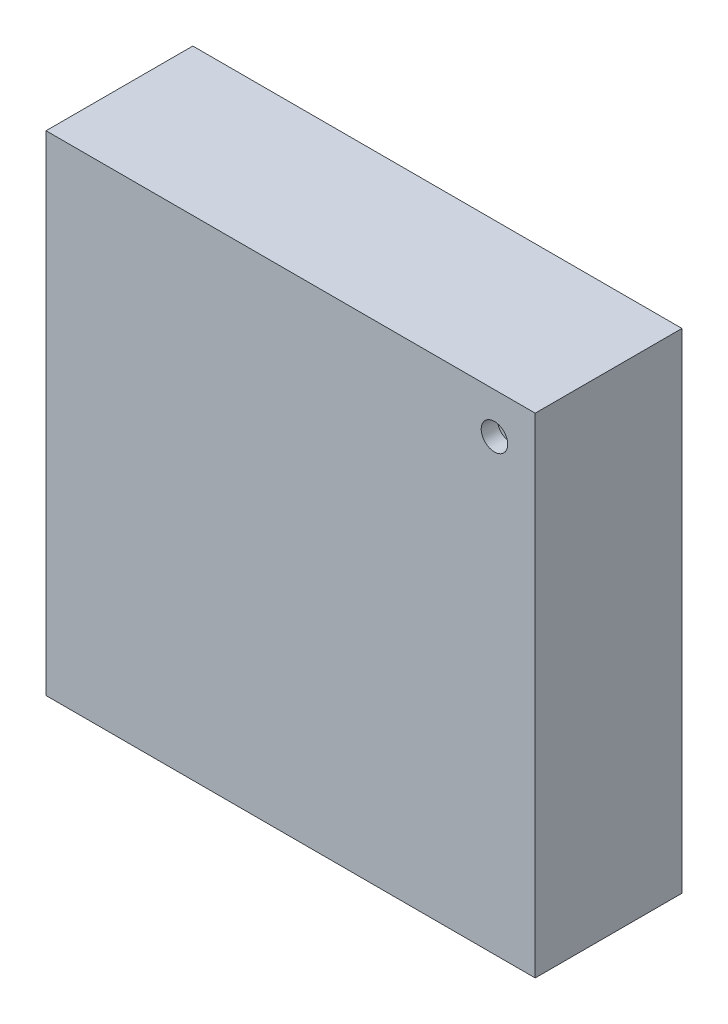
SolidWorks part; units mm, degrees
ref_plane "Front Plane" through (0, 0, 0) normal (0, 0, 1) x (1, 0, 0)
ref_plane "Top Plane" through (0, 0, 0) normal (0, 1, 0) x (1, 0, 0)
ref_plane "Right Plane" through (0, 0, 0) normal (1, 0, 0) x (0, 0, -1)
sketch "Sketch2" plane through (0, 0, 0) normal (0, 0, 1) x (1, 0, 0)
  line L1 (0, 0) -> (3, 0)
  line L2 (0, 0) -> (0, 3)
  line L3 (0, 3) -> (3, 3)
  line L4 (3, 0) -> (3, 3)
  dimension "D1" = 3
  dimension "D2" = 3
extrude "Boss-Extrude1" add sketch "Sketch2" along normal blind 0.9
sketch "Sketch3" plane through (0, 0, 0.9) normal (0, 0, 1) x (1, 0, 0)
  line L0 (3, 0) -> (3, 3) construction
  line L1 (3, 3) -> (0, 3) construction
  circle A0 centre (2.75, 2.75) radius 0.0813
  dimension "D1" = 0.25
  dimension "D2" = 0.25
extrude "Cut-Extrude1" cut sketch "Sketch3" against normal blind 0.1
sketch "Sketch4" plane through (0, 0, 0) normal (0, 0, -1) x (-1, 0, 0)
  line L0 (-3, 0) -> (-3, 3) construction
  line L1 (-2.375, 2.95) -> (-2.125, 2.95)
  line L2 (-2.375, 2.95) -> (-2.375, 2.625)
  line L3 (-2.375, 2.625) -> (-2.125, 2.625)
  line L4 (-2.125, 2.95) -> (-2.125, 2.625)
  line L5 (-3, 3) -> (0, 3) construction
  line L6 (-1.875, 2.95) -> (-1.625, 2.95)
  line L7 (-1.875, 2.95) -> (-1.875, 2.625)
  line L8 (-1.875, 2.625) -> (-1.625, 2.625)
  line L9 (-1.625, 2.95) -> (-1.625, 2.625)
  line L10 (-1.375, 2.95) -> (-1.125, 2.95)
  line L11 (-1.375, 2.95) -> (-1.375, 2.625)
  line L12 (-1.375, 2.625) -> (-1.125, 2.625)
  line L13 (-1.125, 2.95) -> (-1.125, 2.625)
  line L14 (-0.875, 2.95) -> (-0.625, 2.95)
  line L15 (-0.875, 2.95) -> (-0.875, 2.625)
  line L16 (-0.875, 2.625) -> (-0.625, 2.625)
  line L17 (-0.625, 2.95) -> (-0.625, 2.625)
  line L18 (-3, 1.5) -> (0, 1.5) construction
  line L19 (0, 3) -> (0, 0) construction
  line L20 (-0.625, 0.05) -> (-0.625, 0.375)
  line L21 (-0.875, 0.375) -> (-0.625, 0.375)
  line L22 (-0.875, 0.05) -> (-0.875, 0.375)
  line L23 (-0.875, 0.05) -> (-0.625, 0.05)
  line L24 (-1.125, 0.05) -> (-1.125, 0.375)
  line L25 (-1.375, 0.375) -> (-1.125, 0.375)
  line L26 (-1.375, 0.05) -> (-1.375, 0.375)
  line L27 (-1.375, 0.05) -> (-1.125, 0.05)
  line L28 (-1.625, 0.05) -> (-1.625, 0.375)
  line L29 (-1.875, 0.375) -> (-1.625, 0.375)
  line L30 (-1.875, 0.05) -> (-1.875, 0.375)
  line L31 (-1.875, 0.05) -> (-1.625, 0.05)
  line L32 (-2.125, 0.05) -> (-2.125, 0.375)
  line L33 (-2.375, 0.375) -> (-2.125, 0.375)
  line L34 (-2.375, 0.05) -> (-2.375, 0.375)
  line L35 (-2.375, 0.05) -> (-2.125, 0.05)
  dimension "D1" = 0.625
  dimension "D2" = 0.325
  dimension "D3" = 0.25
  dimension "D4" = 0.05
  dimension "D5" = 4
extrude "Boss-Extrude2" add sketch "Sketch4" along normal blind 0.05
ref_plane "Plane1" through (1.5, 1.5, 0) normal (-0.7071, -0.7071, 0) x (-0.7071, 0.7071, 0)
ref_plane "Plane2" through (0, 0, 0) normal (0.7071, -0.7071, 0) x (-0.7071, -0.7071, 0)
ref_axis "Axis1" through (1.5, 1.5, 0.945) along (0, 0, -1)
pattern_circular "CirPattern1" count 2 every 90 about axis through (1.5, 1.5, 0.945) along (0, 0, -1) of "Boss-Extrude2"
